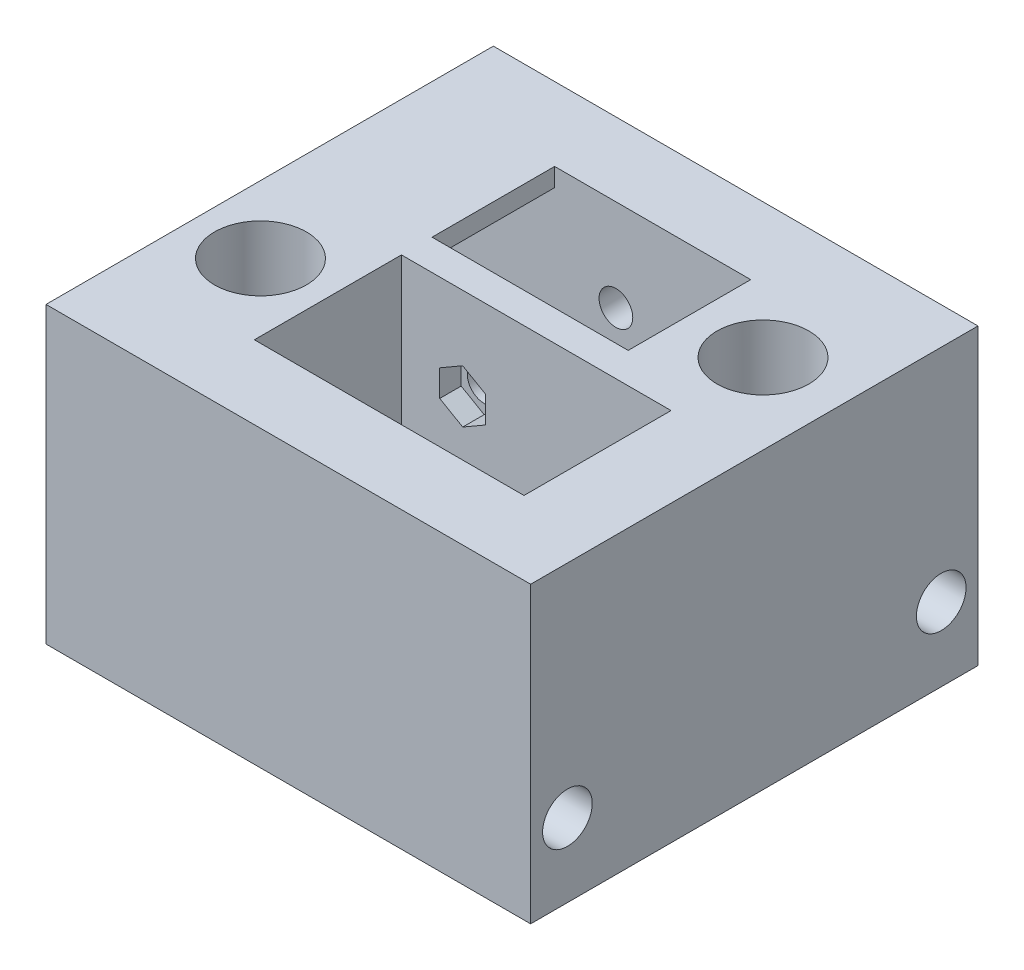
SolidWorks part; units mm, degrees
ref_plane "Front Plane" through (0, 0, 0) normal (0, 0, 1) x (1, 0, 0)
ref_plane "Top Plane" through (0, 0, 0) normal (0, 1, 0) x (1, 0, 0)
ref_plane "Right Plane" through (0, 0, 0) normal (1, 0, 0) x (0, 0, -1)
sketch "Sketch1" plane through (0, 0, 0) normal (0, 1, 0) x (1, 0, 0)
  line L0 (0, 0) -> (0, 24)
  line L1 (0, 24) -> (44, 24)
  line L2 (0, 0) -> (44, 0)
  line L4 (44, -12) -> (-22, -12)
  line L5 (-22, 29) -> (32, 29)
  line L6 (32, 29) -> (32, 49)
  line L7 (44, 61) -> (57.0861, 61)
  line L8 (-22, 29) -> (-22, -12)
  line L11 (0, 12) -> (-11, 12) construction
  line L12 (-11, 12) -> (-22, 12) construction
  line L13 (32, 49) -> (-22, 49)
  line L14 (-22, 49) -> (-22, 61)
  line L15 (-22, 61) -> (44, 61)
  line L17 (57.0861, 61) -> (57.0861, -12)
  line L18 (57.0861, -12) -> (44, -12)
  line L19 (44, 24) -> (44, 0)
  arc A0 (44, 46.5) -> (44, 31.5) centre (44, 39) ccw
  circle A1 centre (-11, 12) radius 7.5
  arc A2 (44, 46.5) -> (44, 31.5) centre (44, 39) cw
  point P15 (22, 24)
  point P18 (32, 39)
  dimension "D8" = 15
  dimension "D10" = 15
  dimension "D1" = 44
  dimension "D2" = 24
  dimension "D3" = 12
  dimension "D4" = 5
  dimension "D5" = 22
  dimension "D6" = 20
  dimension "D7" = 10
  dimension "D9" = 0
  dimension "D11" = 22
  dimension "D12" = 12
extrude "Boss-Extrude1" add sketch "Sketch1" along normal blind 48
sketch "Sketch3" plane through (-22, 0, 0) normal (-1, 0, 0) x (0, 0, 1)
  line L0 (-49, 24) -> (-61, 0) construction
  line L1 (0, 0) -> (12, 24) construction
  line L2 (12, 48) -> (12, 0) construction
  line L3 (-49, 48) -> (-49, 0) construction
  circle A0 centre (-55, 12) radius 4.05
  circle A1 centre (6, 12) radius 4.05
  point P13 (-49, 48)
  point P14 (-49, 24)
  dimension "D1" = 8.1
extrude "Cut-Extrude1" cut sketch "Sketch3" against normal blind 82
sketch "Sketch4" plane through (0, 0, -24) normal (0, 0, 1) x (1, 0, 0)
  line L0 (0, 24) -> (44, 24) construction
  line L1 (0, 48) -> (0, 0) construction
  line L2 (44, 48) -> (44, 0) construction
  line L3 (22, 24) -> (22, 48) construction
  line L4 (0, 48) -> (44, 48) construction
  circle A0 centre (10, 33) radius 2.75
  dimension "D2" = 15
  dimension "D1" = 5.5
  dimension "D3" = 12
extrude "Cut-Extrude2" cut sketch "Sketch4" against normal blind 82
sketch "Sketch6" plane through (0, 48, 0) normal (0, 1, 0) x (1, 0, 0)
  line L0 (32, 29) -> (-22, 29) construction
  line L1 (-22, 49) -> (0, 49)
  line L2 (-22, 49) -> (-22, 29)
  line L3 (-22, 29) -> (0, 29)
  line L4 (0, 49) -> (0, 29)
extrude "Boss-Extrude3" add sketch "Sketch6" against normal blind 3
sketch "Sketch7" plane through (0, 0, 0) normal (0, -1, 0) x (-1, 0, 0)
  line L0 (22, 49) -> (-32, 49) construction
  line L1 (22, 29) -> (0, 29)
  line L2 (22, 29) -> (22, 49)
  line L3 (22, 49) -> (0, 49)
  line L4 (0, 29) -> (0, 49)
extrude "Boss-Extrude4" add sketch "Sketch7" against normal blind 21
sketch "Sketch8" plane through (0, 0, -24) normal (0, 0, 1) x (1, 0, 0)
  line L1 (10, 37.3301) -> (6.25, 35.1651)
  line L2 (6.25, 35.1651) -> (6.25, 30.8349)
  line L3 (6.25, 30.8349) -> (10, 28.6699)
  line L4 (10, 28.6699) -> (13.75, 30.8349)
  line L5 (13.75, 30.8349) -> (13.75, 35.1651)
  line L6 (13.75, 35.1651) -> (10, 37.3301)
  circle A0 centre (10, 33) radius 3.75 construction
  dimension "D1" = 7.5
extrude "Cut-Extrude4" cut sketch "Sketch8" against normal blind 3.5
